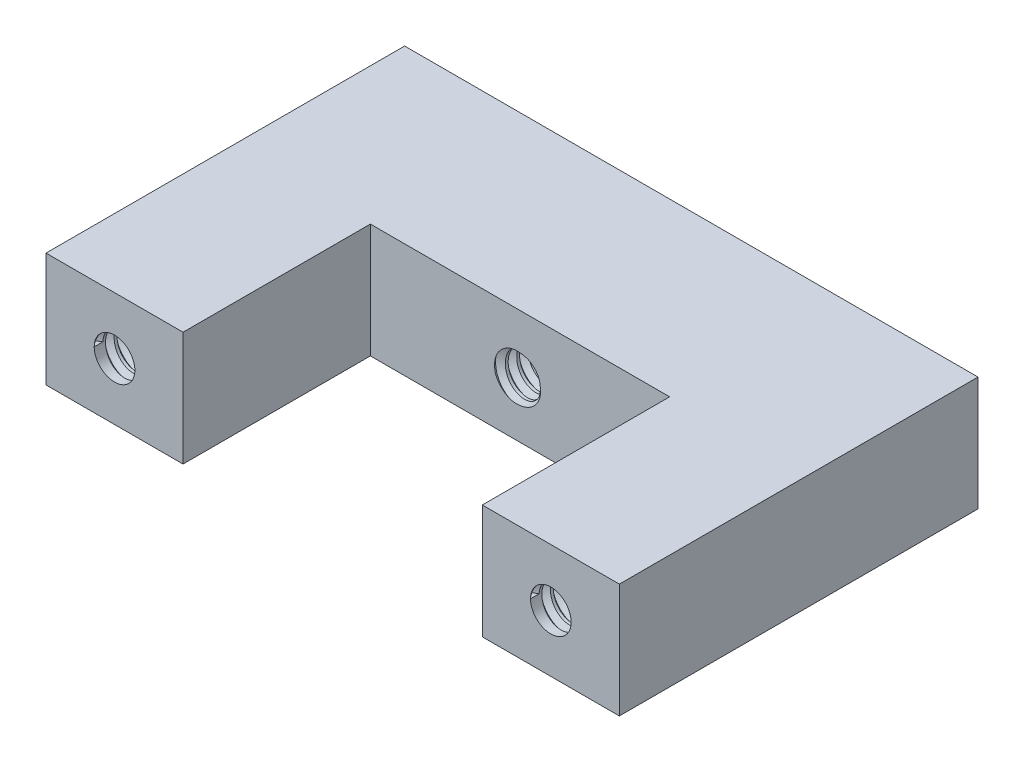
SolidWorks part; units mm, degrees
ref_plane "Front Plane" through (0, 0, 0) normal (0, 0, 1) x (1, 0, 0)
ref_plane "Top Plane" through (0, 0, 0) normal (0, 1, 0) x (1, 0, 0)
ref_plane "Right Plane" through (0, 0, 0) normal (1, 0, 0) x (0, 0, -1)
sketch "Sketch1" plane through (0, 0, 0) normal (0, 1, 0) x (1, 0, 0)
  line L1 (15.9385, -9.9695) -> (-15.9385, -9.9695)
  line L2 (15.9385, -9.9695) -> (15.9385, 9.9695)
  line L3 (15.9385, 9.9695) -> (-15.9385, 9.9695)
  line L4 (-15.9385, -9.9695) -> (-15.9385, 9.9695)
  line L5 (15.9385, -9.9695) -> (-15.9385, 9.9695) construction
  line L6 (15.9385, 9.9695) -> (-15.9385, -9.9695) construction
  line L7 (8.3185, -20.3835) -> (-8.3185, -20.3835)
  line L8 (8.3185, -20.3835) -> (8.3185, 0.4445)
  line L9 (8.3185, 0.4445) -> (-8.3185, 0.4445)
  line L10 (-8.3185, -20.3835) -> (-8.3185, 0.4445)
  line L11 (8.3185, -20.3835) -> (-8.3185, 0.4445) construction
  line L12 (8.3185, 0.4445) -> (-8.3185, -20.3835) construction
  point P0 (0, 0)
  point P6 (0, -9.9695)
  dimension "D1" = 31.877
  dimension "D2" = 19.939
  dimension "D3" = 7.62
  dimension "D4" = 10.414
extrude "Boss-Extrude1" add sketch "Sketch1" along normal blind 6.35 contours L1 L10 L9 L8 L2 L3 L4 region at (0, 0, -1.7847)
hole_wizard "#43 (0.089) Diameter Hole1" positions "Sketch3" profile "Sketch4" hole size "#43" standard "ANSI Inch" end condition through all
sketch "Sketch3" plane through (0, 0, -9.9695) normal (0, 0, -1) x (-1, 0, 0)
  point P0 (0, 3.1752)
sketch "Sketch4" plane through (0, 3.1752, -9.9695) normal (1, 0, 0) x (0, 1, 0)
  line L0 (0, 0) -> (0, 19.939)
  line L1 (0, 19.939) -> (1.1303, 19.939)
  line L2 (1.1303, 19.939) -> (1.1303, 0)
  line L5 (1.1303, 0) -> (0, 0)
  line L11 (0, -6.35) -> (0, 107.95) construction
  dimension "Thru Hole Dia." = 2.2606
  dimension "Thru Hole Depth" = 19.939
thread "Thread1" pitch 0.635 method cut profile "Thread Profile1" start angle 0, offset 0, length 15.7163, pitch 0.635, diameter 2.2606
ref_plane "Plane1" through (1.1303, 3.1752, -9.9695) normal (0, -1, 0) x (1, 0, 0)
sketch "Thread Profile1" plane through (1.1303, 3.1752, -9.9695) normal (0, -1, 0) x (1, 0, 0)
  line L0 (0, 0) -> (0, 0.635) construction
  line L1 (0, 0) -> (0.3437, 0.1984)
  line L2 (0.3437, 0.1984) -> (0.3437, 0.2778)
  line L3 (0.3437, 0.2778) -> (0, 0.4762)
  line L4 (0.3437, 0.2381) -> (0, 0.2381) construction
  line L11 (0, 0) -> (0, 0.4762)
  point P2 (0, 0)
  dimension "Pitch" = 0.635
  dimension "Profile_Angle" = 60
  dimension "Profile_Land" = 0.0794
  dimension "Profile_Height" = 0.3437
hole_wizard "#43 (0.089) Diameter Hole2" positions "Sketch8" profile "Sketch9" hole size "#43" standard "ANSI Inch"
sketch "Sketch8" plane through (0, 0, 9.9695) normal (0, 0, 1) x (1, 0, 0)
  line L0 (-15.9385, 6.35) -> (-15.9385, 0) construction
  line L1 (15.9385, 6.35) -> (15.9385, 0) construction
  line L2 (15.9385, 0) -> (8.3185, 0) construction
  line L3 (-8.3185, 0) -> (-15.9385, 0) construction
  point P0 (12.1285, 3.175)
  point P2 (-12.1285, 3.175)
  dimension "D1" = 3.81
  dimension "D2" = 3.81
  dimension "D3" = 3.175
  dimension "D4" = 3.175
sketch "Sketch9" plane through (12.1285, 3.175, 9.9695) normal (1, 0, 0) x (0, -1, 0)
  line L0 (0, 0) -> (0, 8.2992)
  line L1 (0, 8.2992) -> (1.1303, 7.62)
  line L2 (1.1303, 7.62) -> (1.1303, 0)
  line L5 (1.1303, 0) -> (0, 0)
  line L10 (0, 8.2992) -> (-1.1303, 7.62) construction
  line L11 (0, -6.35) -> (0, 107.95) construction
  dimension "Hole Dia." = 2.2606
  dimension "Hole Depth" = 7.62
  dimension "Drill Angle" = 118
thread "Thread2" pitch 0.635 method cut profile "Thread Profile2" start angle 0, offset 0, length 5.5562, pitch 0.635, diameter 2.2606
ref_plane "Plane2" through (-13.2588, 3.175, 9.9695) normal (0, -1, 0) x (-1, 0, 0)
sketch "Thread Profile2" plane through (-13.2588, 3.175, 9.9695) normal (0, -1, 0) x (-1, 0, 0)
  line L0 (0, 0) -> (0, 0.635) construction
  line L1 (0, 0) -> (0.3437, 0.1984)
  line L2 (0.3437, 0.1984) -> (0.3437, 0.2778)
  line L3 (0.3437, 0.2778) -> (0, 0.4762)
  line L4 (0.3437, 0.2381) -> (0, 0.2381) construction
  line L11 (0, 0) -> (0, 0.4762)
  point P2 (0, 0)
  dimension "Pitch" = 0.635
  dimension "Profile_Angle" = 60
  dimension "Profile_Land" = 0.0794
  dimension "Profile_Height" = 0.3437
thread "Thread3" pitch 0.635 method cut profile "Thread Profile3" start angle 0, offset 0, length 5.5562, pitch 0.635, diameter 2.2606
ref_plane "Plane3" through (10.9982, 3.175, 9.9695) normal (0, -1, 0) x (-1, 0, 0)
sketch "Thread Profile3" plane through (10.9982, 3.175, 9.9695) normal (0, -1, 0) x (-1, 0, 0)
  line L0 (0, 0) -> (0, 0.635) construction
  line L1 (0, 0) -> (0.3437, 0.1984)
  line L2 (0.3437, 0.1984) -> (0.3437, 0.2778)
  line L3 (0.3437, 0.2778) -> (0, 0.4762)
  line L4 (0.3437, 0.2381) -> (0, 0.2381) construction
  line L11 (0, 0) -> (0, 0.4762)
  point P2 (0, 0)
  dimension "Pitch" = 0.635
  dimension "Profile_Angle" = 60
  dimension "Profile_Land" = 0.0794
  dimension "Profile_Height" = 0.3437
